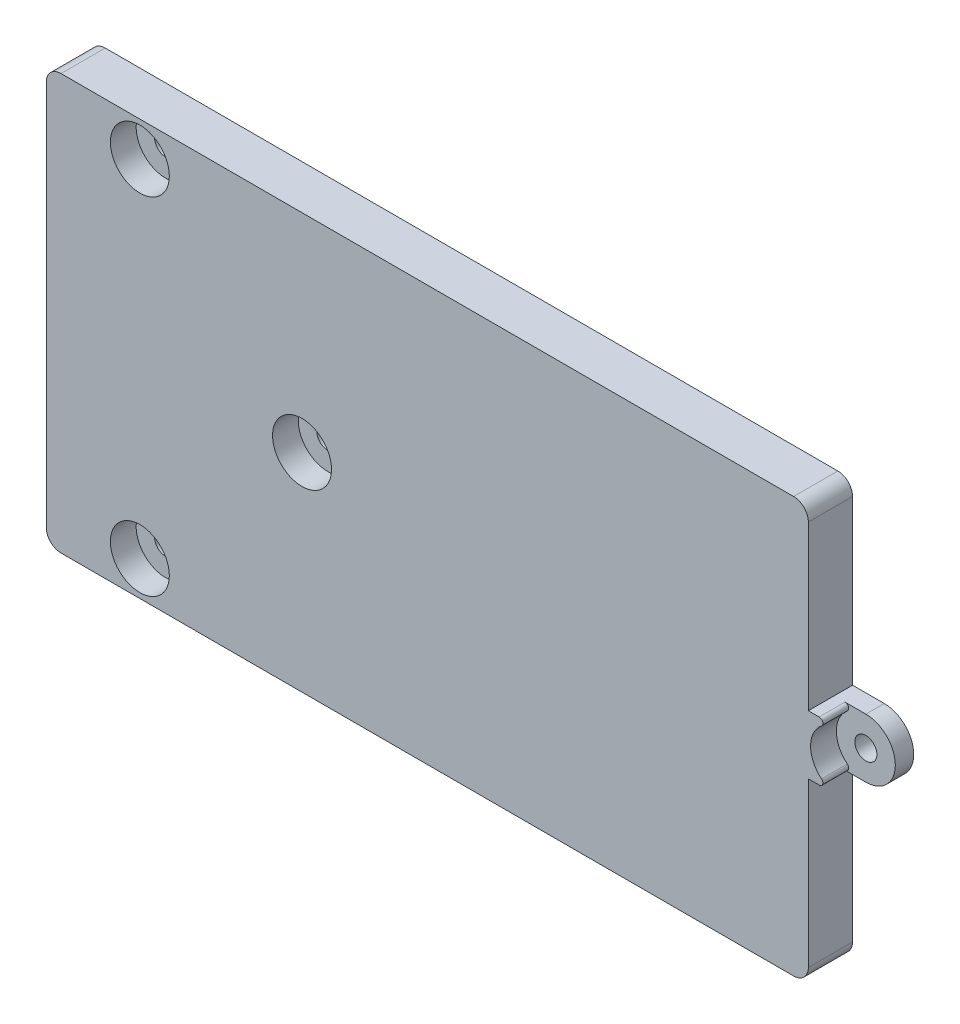
SolidWorks part; units mm, degrees
ref_plane "Front Plane" through (0, 0, 0) normal (0, 0, 1) x (1, 0, 0)
ref_plane "Top Plane" through (0, 0, 0) normal (0, 1, 0) x (1, 0, 0)
ref_plane "Right Plane" through (0, 0, 0) normal (1, 0, 0) x (0, 0, -1)
sketch "Sketch1" plane through (0, 0, 0) normal (0, 0, 1) x (1, 0, 0)
  line L1 (26, -14.235) -> (-26, -14.235)
  line L2 (26, -14.235) -> (26, 14.235)
  line L3 (26, 14.235) -> (-26, 14.235)
  line L4 (-26, -14.235) -> (-26, 14.235)
  line L5 (26, -14.235) -> (-26, 14.235) construction
  line L6 (26, 14.235) -> (-26, -14.235) construction
  line L7 (26, 2) -> (30, 2)
  line L8 (26, 2) -> (26, -2)
  line L9 (26, -2) -> (30, -2)
  line L10 (30, 2) -> (30, -2)
  circle A0 centre (28, 0) radius 2
  point P0 (0, 0)
  dimension "D1" = 52
  dimension "D2" = 28.47
  dimension "D3" = 4
  dimension "D4" = 4
  dimension "D5" = 2
extrude "Boss-Extrude1" add sketch "Sketch1" along normal blind 1.5 and the other way blind 1.5 contours L4 L1 L2 L3 | A0 | A0 L2 L9 | A0 L7 L8 region at (0, 0, 0) region at (26.4467, -1.5533, 0) region at (26.4467, 1.5533, 0) region at (28, 0, 0)
sketch "Sketch2" plane through (0, 0, 1.5) normal (0, 0, 1) x (1, 0, 0)
  line L0 (-26, -14.235) -> (-26, 14.235) construction
  line L1 (26, 14.235) -> (-26, 14.235) construction
  line L2 (26, -14.235) -> (-26, -14.235) construction
  line L4 (26, 2) -> (28, 2) construction
  line L5 (26, 2) -> (26, 14.235) construction
  line L6 (26, -14.235) -> (26, -2) construction
  line L7 (-8.5, 0) -> (28, 0) construction
  circle A0 centre (-19.5, 11.735) radius 0.75
  circle A1 centre (20.4, 11.735) radius 0.75 construction
  circle A2 centre (-8.5, 0) radius 0.75
  circle A3 centre (-19.5, -11.735) radius 0.75
  circle A4 centre (20.4, -11.735) radius 0.75 construction
  circle A5 centre (28, 0) radius 0.75
  dimension "D2" = 1.5
  dimension "D3" = 1.5
  dimension "D4" = 1.5
  dimension "D5" = 1.5
  dimension "D6" = 1.5
  dimension "D7" = 1.5
  dimension "D1" = 6.5
  dimension "D8" = 2.5
  dimension "D9" = 6.5
  dimension "D10" = 2.5
  dimension "D11" = 2.5
  dimension "D12" = 2.5
  dimension "D13" = 2
  dimension "D14" = 2
  dimension "D15" = 5.6
  dimension "D16" = 5.6
  dimension "D17" = 17.5
extrude "Cut-Extrude1" cut sketch "Sketch2" against normal blind 9.5
sketch "Sketch3" plane through (0, 0, 1.5) normal (0, 0, 1) x (1, 0, 0)
  circle A0 centre (-8.5, 0) radius 0.75 construction
  circle A1 centre (-19.5, 11.735) radius 0.75 construction
  circle A2 centre (-8.5, 0) radius 0.75
  circle A3 centre (-19.5, 11.735) radius 0.75
  circle A4 centre (-19.5, -11.735) radius 0.75 construction
  circle A7 centre (-19.5, -11.735) radius 0.75
  circle A10 centre (-19.5, 11.735) radius 2
  circle A11 centre (-8.5, 0) radius 2
  circle A12 centre (-19.5, -11.735) radius 2
  circle A13 centre (13.4, 11.735) radius 2 construction
  circle A14 centre (13.4, -11.735) radius 2 construction
  circle A15 centre (28, 0) radius 0.75 construction
  circle A16 centre (28, 0) radius 0.75
  circle A17 centre (28, 0) radius 2
  dimension "D1" = 4
  dimension "D2" = 4
  dimension "D3" = 4
  dimension "D4" = 4
  dimension "D5" = 4
  dimension "D6" = 4
extrude "Cut-Extrude2" cut sketch "Sketch3" against normal blind 1.75
fillet "Fillet1" radius 0.25 2 edges at (28, -2, 0.625) (28, 2, 0.625)
sketch "Sketch4" plane through (0, 0, 1.5) normal (0, 0, 1) x (1, 0, 0)
  line L1 (-26, 6) -> (-34, 6)
  line L2 (-26, 6) -> (-26, -6)
  line L3 (-26, -6) -> (-34, -6)
  line L4 (-34, 6) -> (-34, -6)
  line L7 (26, -2) -> (26.5858, -2)
  line L8 (26.5858, 2) -> (26, 2)
  line L9 (26, 2) -> (26, 14.235)
  line L10 (26, 14.235) -> (-26, 14.235)
  line L11 (-26, 14.235) -> (-26, -14.235)
  line L12 (-26, -14.235) -> (26, -14.235)
  line L13 (26, -14.235) -> (26, -2)
  line L14 (26, -2) -> (26.5858, -2)
  line L15 (26.5858, 2) -> (26, 2)
  line L16 (26, 2) -> (26, 14.235)
  line L17 (26, 14.235) -> (-26, 14.235)
  line L18 (-26, 14.235) -> (-26, -14.235)
  line L19 (-26, -14.235) -> (26, -14.235)
  line L20 (26, -14.235) -> (26, -2)
  arc A3 (26.5858, -2) -> (26.7429, -1.5556) centre (26.5858, -1.75) ccw
  arc A4 (26.7429, 1.5556) -> (26.7429, -1.5556) centre (28, 0) ccw
  arc A5 (26.7429, 1.5556) -> (26.5858, 2) centre (26.5858, 1.75) ccw
  arc A6 (26.5858, -2) -> (26.7429, -1.5556) centre (26.5858, -1.75) ccw
  arc A7 (26.7429, 1.5556) -> (26.7429, -1.5556) centre (28, 0) ccw
  arc A8 (26.7429, 1.5556) -> (26.5858, 2) centre (26.5858, 1.75) ccw
  line M24 (-26, 14.235) -> (-26, -14.235)
  dimension "D2" = 12
  dimension "D3" = 8
  dimension "D4" = 6
  dimension "D1" = 0
extrude "Boss-Extrude2" [suppressed] add sketch "Sketch4" against normal up to surface (3 mm away) contours L1 L4 L3 M24
sketch "Sketch5" plane through (0, 14.235, 0) normal (0, 1, 0) x (1, 0, 0)
  line L4 (-26, 1.5) -> (-26, -1.5)
  line L5 (-26, -1.5) -> (26, -1.5)
  line L6 (26, -1.5) -> (26, 1.5)
  line L7 (26, 1.5) -> (-26, 1.5)
  line L8 (-26, 1.5) -> (-26, -1.5)
  line L9 (-26, -1.5) -> (26, -1.5)
  line L10 (26, -1.5) -> (26, 1.5)
  line L11 (26, 1.5) -> (-26, 1.5)
  circle A0 centre (-21.95, 2.5) radius 2.25
  dimension "D4" = 4.5
  dimension "D2" = 1
  dimension "D3" = 4.05
  dimension "D1" = 0
extrude "Cut-Extrude3" [suppressed] cut sketch "Sketch5" against normal blind 18 contours L11 A0
sketch "Sketch6" plane through (0, -14.235, 0) normal (0, -1, 0) x (1, 0, 0)
  line L4 (26, -1.5) -> (26, 1.5)
  line L5 (26, 1.5) -> (-26, 1.5)
  line L6 (-26, 1.5) -> (-26, -1.5)
  line L7 (-26, -1.5) -> (26, -1.5)
  line L8 (26, -1.5) -> (26, 1.5)
  line L9 (26, 1.5) -> (-26, 1.5)
  line L10 (-26, 1.5) -> (-26, -1.5)
  line L11 (-26, -1.5) -> (26, -1.5)
  circle A0 centre (-27.15, -2.5) radius 2.25
  line M8 (-26, -1.5) -> (26, -1.5)
  dimension "D4" = 4.5
  dimension "D2" = 1.15
  dimension "D3" = 1
  dimension "D1" = 0
extrude "Cut-Extrude4" [suppressed] cut sketch "Sketch6" against normal blind 18 contours L10 A0 M8 | A0 L10 M8
sketch "Sketch7" plane through (0, 0, 1.5) normal (0, 0, 1) x (1, 0, 0)
  line L11 (26, -2) -> (26.5858, -2)
  line L12 (26.5858, 2) -> (26, 2)
  line L13 (26, 2) -> (26, 14.235)
  line L14 (26, 14.235) -> (-26, 14.235)
  line L15 (-26, 14.235) -> (-26, -14.235)
  line L16 (25.85, 2) -> (25.85, 14.085)
  line L17 (25.85, 14.085) -> (-25.85, 14.085)
  line L18 (-25.85, 14.085) -> (-25.85, -14.085)
  line L19 (-25.85, -14.085) -> (25.85, -14.085)
  line L20 (-26, -14.235) -> (26, -14.235)
  line L21 (26, -14.235) -> (26, -2)
  line L22 (26, -2) -> (26.5858, -2)
  line L23 (26.5858, 2) -> (26, 2)
  line L24 (26, 2) -> (26, 14.235)
  line L25 (26, 14.235) -> (-26, 14.235)
  line L26 (-26, 14.235) -> (-26, -14.235)
  line L31 (-26, -14.235) -> (26, -14.235)
  line L32 (26, -14.235) -> (26, -2)
  line L33 (26, 2) -> (25.79, 2)
  line L34 (26, -2) -> (25.79, -2)
  line L35 (25.85, -14.085) -> (25.85, -2)
  arc A3 (26.5858, -2) -> (26.7429, -1.5556) centre (26.5858, -1.75) ccw
  arc A4 (26.7429, 1.5556) -> (26.7429, -1.5556) centre (28, 0) ccw
  arc A5 (26.7429, 1.5556) -> (26.5858, 2) centre (26.5858, 1.75) ccw
  arc A6 (26.5858, -2) -> (26.7429, -1.5556) centre (26.5858, -1.75) ccw
  arc A7 (26.7429, 1.5556) -> (26.7429, -1.5556) centre (28, 0) ccw
  arc A8 (26.7429, 1.5556) -> (26.5858, 2) centre (26.5858, 1.75) ccw
  line M37 (26, 2) -> (26, 14.235)
  line M38 (26, 14.235) -> (-26, 14.235)
  line M39 (-26, 14.235) -> (-26, -14.235)
  line M43 (-26, 14.235) -> (-26, -14.235)
  line M44 (-26, -14.235) -> (26, -14.235)
  line M45 (26, -14.235) -> (26, -2)
  dimension "D1" = 0
  dimension "D2" = 0.15
extrude "Cut-Extrude5" cut sketch "Sketch7" against normal blind 7 contours L34 L33 M45 M37 M38 M39 M43 M44 region at (25.9407, -8.1175, 1.5)
sketch "Sketch8" plane through (-25.85, 0, 0) normal (-1, 0, 0) x (0, 0, 1)
  line L0 (1.5, 14.085) -> (1.5, -14.085) construction
  line L1 (-7.5, 0) -> (0, 0) construction
  line L5 (-1.5, 14.085) -> (-1.5, -14.085)
  line L6 (-1.5, -14.085) -> (1.5, -14.085)
  line L7 (1.5, -14.085) -> (1.5, 14.085)
  line L8 (1.5, 14.085) -> (-1.5, 14.085)
  line L9 (-1.5, 14.085) -> (-1.5, -14.085)
  line L10 (-1.5, -14.085) -> (1.5, -14.085)
  line L11 (1.5, -14.085) -> (1.5, 14.085)
  line L12 (1.5, 14.085) -> (-1.5, 14.085)
  circle A0 centre (-7.5, 0) radius 6.6
  line M5 (-1.5, 14.085) -> (-1.5, -14.085)
  dimension "D1" = 13.2
  dimension "D2" = 9
  dimension "D3" = 0
extrude "Cut-Extrude6" cut sketch "Sketch8" against normal blind 15 contours L9 L1 A0 | L1 A0 M5 region at (-25.85, 1.0376, -1.259) region at (-25.85, -1.0376, -1.259)
fillet "Fillet2" radius 1 4 edges at (25.85, -14.085, 0) (25.85, 14.085, 0) (-25.85, 14.085, 0) (-25.85, -14.085, 0)
